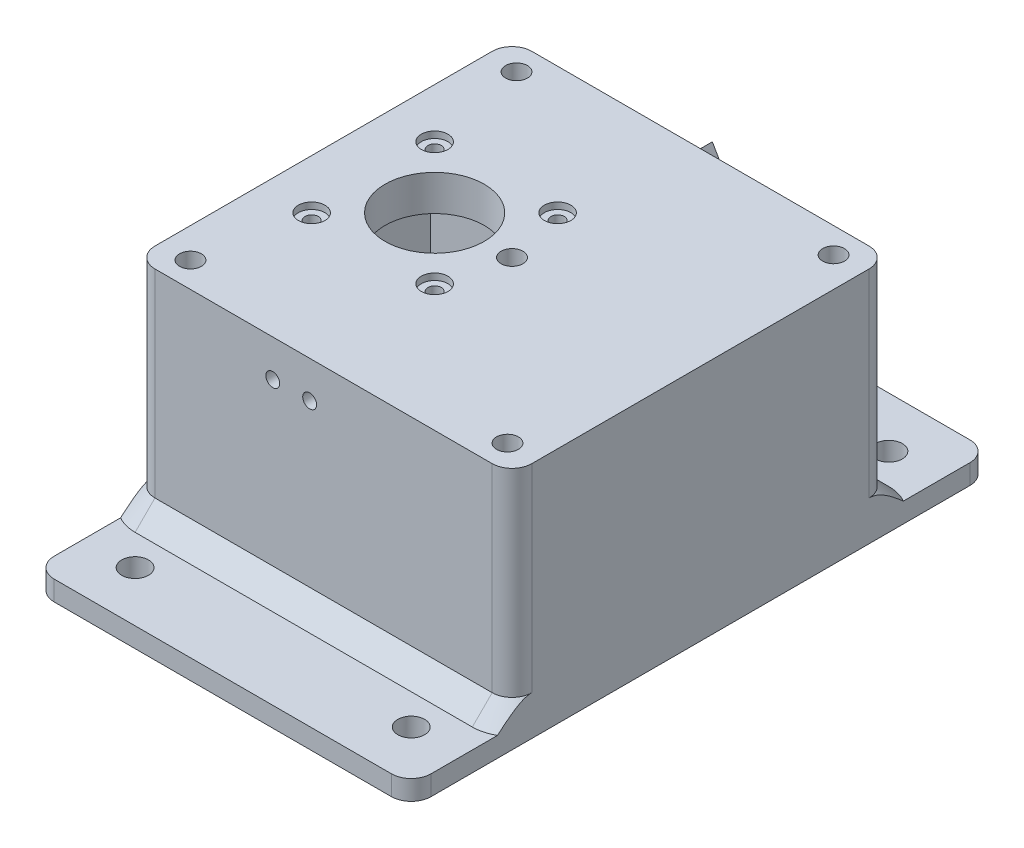
SolidWorks part; units mm, degrees
ref_plane "Front Plane" through (0, 0, 0) normal (0, 0, 1) x (1, 0, 0)
ref_plane "Top Plane" through (0, 0, 0) normal (0, 1, 0) x (1, 0, 0)
ref_plane "Right Plane" through (0, 0, 0) normal (1, 0, 0) x (0, 0, -1)
sketch "Sketch1" plane through (0, 0, 0) normal (0, 1, 0) x (1, 0, 0)
  line L1 (-47.5, -47.5) -> (47.5, -47.5)
  line L2 (-47.5, -47.5) -> (-47.5, 47.5)
  line L3 (-47.5, 47.5) -> (47.5, 47.5)
  line L4 (47.5, -47.5) -> (47.5, 47.5)
  line L5 (-47.5, -47.5) -> (47.5, 47.5) construction
  line L6 (-47.5, 47.5) -> (47.5, -47.5) construction
  point P0 (0, 0)
  dimension "D1" = 95
  dimension "D2" = 95
extrude "Boss-Extrude1" add sketch "Sketch1" along normal blind 60
sketch "Sketch2" plane through (0, 0, 47.5) normal (0, 0, 1) x (1, 0, 0)
  line L0 (47.5, 60) -> (47.5, 0) construction
  line L1 (-47.5, 0) -> (47.5, 0)
  line L2 (-47.5, 0) -> (-47.5, 5)
  line L3 (-47.5, 5) -> (47.5, 5)
  line L4 (47.5, 0) -> (47.5, 5)
  dimension "D1" = 5
extrude "Boss-Extrude2" add sketch "Sketch2" along normal blind 25.4
mirror "Mirror1" about plane through (0, 0, 0) normal (0, 0, 1) of "Boss-Extrude2"
fillet "Fillet1" radius 5 8 edges at (47.5, 2.5, -72.9) (-47.5, 2.5, -72.9) (-47.5, 32.5, 47.5) (-47.5, 2.5, 72.9) (47.5, 2.5, 72.9) (47.5, 32.5, 47.5) (47.5, 32.5, -47.5) (-47.5, 32.5, -47.5)
hole_wizard "1/4 Clearance Hole1" positions "Sketch3" profile "Sketch4" hole size "1/4" standard "ANSI Inch"
sketch "Sketch3" plane through (0, 5, 0) normal (0, 1, 0) x (1, 0, 0)
  line L0 (-47.5, -60.2) -> (47.5, -60.2)
  line L1 (-47.5, -67.9) -> (-47.5, -42.5) construction
  line L2 (47.5, -67.9) -> (47.5, -42.5) construction
  line L4 (42.5, -47.5) -> (-42.5, -47.5) construction
  point P11 (-34.8, -60.2)
  point P13 (34.8, -60.2)
  dimension "D1" = 12.7
  dimension "D2" = 12.7
  dimension "D3" = 12.7
sketch "Sketch4" plane through (34.8, 5, 60.2) normal (1, 0, 0) x (0, 0, 1)
  line L0 (0, 0) -> (0, 12.0298)
  line L1 (0, 12.0298) -> (3.3782, 10)
  line L2 (3.3782, 10) -> (3.3782, 0)
  line L5 (3.3782, 0) -> (0, 0)
  line L10 (0, 12.0298) -> (-3.3782, 10) construction
  line L11 (0, -6.35) -> (0, 107.95) construction
  dimension "Hole Dia." = 6.7564
  dimension "Hole Depth" = 10
  dimension "Drill Angle" = 118
mirror "Mirror2" about plane through (0, 0, 0) normal (0, 0, 1) of "1/4 Clearance Hole1"
sketch "Sketch5" plane through (0, 0, -47.5) normal (0, 0, -1) x (-1, 0, 0)
  line L0 (0, 60) -> (-2.8868, 55)
  line L1 (-42.5, 60) -> (42.5, 60) construction
  line L2 (-2.8868, 55) -> (2.8868, 55)
  line L3 (2.8868, 55) -> (0, 60)
  line L4 (-42.5, 5) -> (42.5, 5) construction
  point P5 (0.5645, 60)
  point P8 (0, 5)
  dimension "D1" = 60
  dimension "D2" = 60
  dimension "D3" = 5
extrude "Boss-Extrude3" add sketch "Sketch5" along normal blind 3
chamfer "Chamfer1" distance 5 angle 31 1 edges at (0, 55, -47.5) first distance on face at (0, 45, -47.5)
sketch "Sketch6" plane through (0, 0, 0) normal (0, -1, 0) x (1, 0, 0)
  line L0 (-47.5, -67.9) -> (-47.5, 67.9) construction
  line L1 (-47.5, -22) -> (2.5, -22)
  line L2 (-47.5, -22) -> (-47.5, 22)
  line L3 (-47.5, 22) -> (2.5, 22)
  line L4 (2.5, -22) -> (2.5, 22)
  line L6 (2.5, -22) -> (-41.5, -22)
  line L7 (2.5, -22) -> (2.5, 22)
  line L8 (2.5, 22) -> (-41.5, 22)
  line L9 (-41.5, -22) -> (-41.5, 22)
  circle A0 centre (-19.5, 0) radius 12.5
  point P6 (2.5, 0)
  point P11 (-41.5, 0)
  point P14 (0, 0)
  line M19 (-47.5, 67.9) -> (-47.5, -67.9)
  dimension "D5" = 25
  dimension "D1" = 44
  dimension "D2" = 44
  dimension "D3" = 50
  dimension "D4" = 22
extrude "Cut-Extrude1" cut sketch "Sketch6" against normal blind 51 contours L1 L9 L3 M19 | L9 L1 L4 L3 A0 | A0 region at (-44.5, 0, 0) region at (-40.8777, 0, 0)
extrude "Cut-Extrude2" cut sketch "Sketch6<3>" against normal through all contours A0 region at (-19.5, 0, 0)
sketch "Sketch6<3>" plane through (0, 0, 0) normal (0, -1, 0) x (1, 0, 0) same geometry as "Sketch6"
sketch "Sketch7" plane through (0, 51, 0) normal (0, -1, 0) x (1, 0, 0)
  line L0 (-47.5, 22) -> (2.5, 22) construction
  line L1 (-47.5, -22) -> (-42.5, -22)
  line L2 (-47.5, -22) -> (-47.5, 22)
  line L3 (-47.5, 22) -> (-42.5, 22)
  line L4 (-42.5, -22) -> (-42.5, 22)
  dimension "D1" = 5
extrude "Boss-Extrude4" add sketch "Sketch7" along normal blind 27
sketch "Sketch8" plane through (0, 24, 0) normal (0, -1, 0) x (1, 0, 0)
  line L0 (-47.5, 22) -> (-47.5, -22) construction
  line L1 (-42.5, -22) -> (-47.5, -22)
  line L2 (-42.5, -22) -> (-42.5, -9.5)
  line L3 (-42.5, -9.5) -> (-47.5, -9.5)
  line L4 (-47.5, -22) -> (-47.5, -9.5)
  line L6 (-42.5, 22) -> (-47.5, 22)
  line L7 (-42.5, 22) -> (-42.5, 9.5)
  line L8 (-42.5, 9.5) -> (-47.5, 9.5)
  line L9 (-47.5, 22) -> (-47.5, 9.5)
  dimension "D1" = 12.5
extrude "Boss-Extrude5" add sketch "Sketch8" along normal blind 24
hole_wizard "CBORE for M3 SBHCS1" positions "Sketch9" profile "Sketch11" counterbore size "M3" standard "ANSI Metric" end condition through all
sketch "Sketch9" plane through (0, 60, 0) normal (0, 1, 0) x (1, 0, 0)
  line L1 (-35, 15.5) -> (-4, 15.5)
  line L2 (-35, 15.5) -> (-35, -15.5)
  line L3 (-35, -15.5) -> (-4, -15.5)
  line L4 (-4, 15.5) -> (-4, -15.5)
  line L5 (-35, 15.5) -> (-4, -15.5) construction
  line L6 (-35, -15.5) -> (-4, 15.5) construction
  circle A2 centre (-19.5, 0) radius 12.5 construction
  circle A3 centre (-19.5, 0) radius 12.5
  point P1 (-19.5, 0)
  point P2 (-4, -15.5)
  point P75 (-35, 15.5)
  point P76 (-35, -15.5)
  point P77 (-4, 15.5)
  point P95 (0, 0)
  point P96 (-19.5, 0)
  point P97 (-34.0219, -22.9801)
  point P98 (-19.5, 0)
  dimension "D1" = 31
  dimension "D2" = 31
sketch "Sketch11" plane through (-19.5, 60, 0) normal (1, 0, 0) x (0, 0, 1)
  line L0 (0, 0) -> (0, 60)
  line L1 (0, 60) -> (1.7, 60)
  line L3 (1.7, 60) -> (1.7, 1.65)
  line L4 (1.7, 1.65) -> (3.35, 1.65)
  line L5 (3.35, 1.65) -> (3.35, 0)
  line L7 (3.35, 0) -> (0, 0)
  line L11 (0, -6.35) -> (0, 107.95) construction
  dimension "Thru Hole Dia." = 3.4
  dimension "Thru Hole Depth" = 60
  dimension "C'Bore Dia." = 6.7
  dimension "C'Bore Depth" = 1.65
sketch "Sketch13" plane through (0, 0, 0) normal (1, 0, 0) x (0, 0, -1)
  line L0 (72.9, 5) -> (47.5, 5)
  line L1 (72.9, 5) -> (47.5, 5) construction
  line L2 (47.5, 50) -> (47.5, 5)
  line L3 (47.5, 50) -> (47.5, 5) construction
  line L4 (47.5, 13) -> (55.5, 5)
  line L5 (55.5, 5) -> (47.5, 5)
  line L6 (47.5, 5) -> (47.5, 13)
  dimension "D1" = 45
  dimension "D2" = 8
chamfer "Chamfer2" distance 5 angle 45 6 edges at (46.0355, 5, 46.0355) (-46.0355, 5, 46.0355) (0, 5, 47.5) (46.0355, 5, -46.0355) (-46.0355, 5, -46.0355) (0, 5, -47.5)
chamfer "Chamfer3" distance 5 angle 45 2 edges at (-45, 0, 9.5) (-45, 0, -9.5)
hole_wizard "Ø6.0mm Dowel Hole1" positions "Sketch14" profile "Sketch16" hole size "Ø6.0" standard "ANSI Metric"
sketch "Sketch14" plane through (0, 60, 0) normal (0, 1, 0) x (1, 0, 0)
  line L1 (-39.9523, -41.0937) -> (39.9523, -41.0937)
  line L2 (-39.9523, -41.0937) -> (-39.9523, 41.0937)
  line L3 (-39.9523, 41.0937) -> (39.9523, 41.0937)
  line L4 (39.9523, -41.0937) -> (39.9523, 41.0937)
  line L5 (-39.9523, -41.0937) -> (39.9523, 41.0937) construction
  line L6 (-39.9523, 41.0937) -> (39.9523, -41.0937) construction
  point P1 (0, 0)
  point P2 (39.9523, 41.0937)
  point P69 (-39.9523, -41.0937)
  point P70 (-39.9523, 41.0937)
  point P71 (39.9523, -41.0937)
sketch "Sketch16" plane through (0, 60, 0) normal (1, 0, 0) x (0, 0, 1)
  line L0 (0, 0) -> (0, 13.6524)
  line L1 (0, 13.6524) -> (2.75, 12)
  line L2 (2.75, 12) -> (2.75, 0)
  line L5 (2.75, 0) -> (0, 0)
  line L10 (0, 13.6524) -> (-2.75, 12) construction
  line L11 (0, -6.35) -> (0, 107.95) construction
  dimension "Hole Dia." = 5.5
  dimension "Hole Depth" = 12
  dimension "Drill Angle" = 118
hole_wizard "Ø3.0mm Dowel Hole1" positions "Sketch17" profile "Sketch18" hole size "Ø3.0" standard "ANSI Metric"
sketch "Sketch17" plane through (0, 0, 47.5) normal (0, 0, 1) x (1, 0, 0)
  line L0 (0, 60) -> (0, 10) construction
  line L1 (-42.5, 60) -> (42.5, 60) construction
  line L2 (-42.5, 10) -> (42.5, 10) construction
  point P0 (-3.5, 50.7)
  point P2 (-12.8, 50.7)
  point P13 (-12.8, 52.6309)
  dimension "D1" = 3.5
  dimension "D2" = 9.3
  dimension "D3" = 9.3
sketch "Sketch18" plane through (-3.5, 50.7, 47.5) normal (1, 0, 0) x (0, -1, 0)
  line L0 (0, 0) -> (0, 13.0515)
  line L1 (0, 13.0515) -> (1.75, 12)
  line L2 (1.75, 12) -> (1.75, 0)
  line L5 (1.75, 0) -> (0, 0)
  line L10 (0, 13.0515) -> (-1.75, 12) construction
  line L11 (0, -6.35) -> (0, 107.95) construction
  dimension "Hole Dia." = 3.5
  dimension "Hole Depth" = 12
  dimension "Drill Angle" = 118
